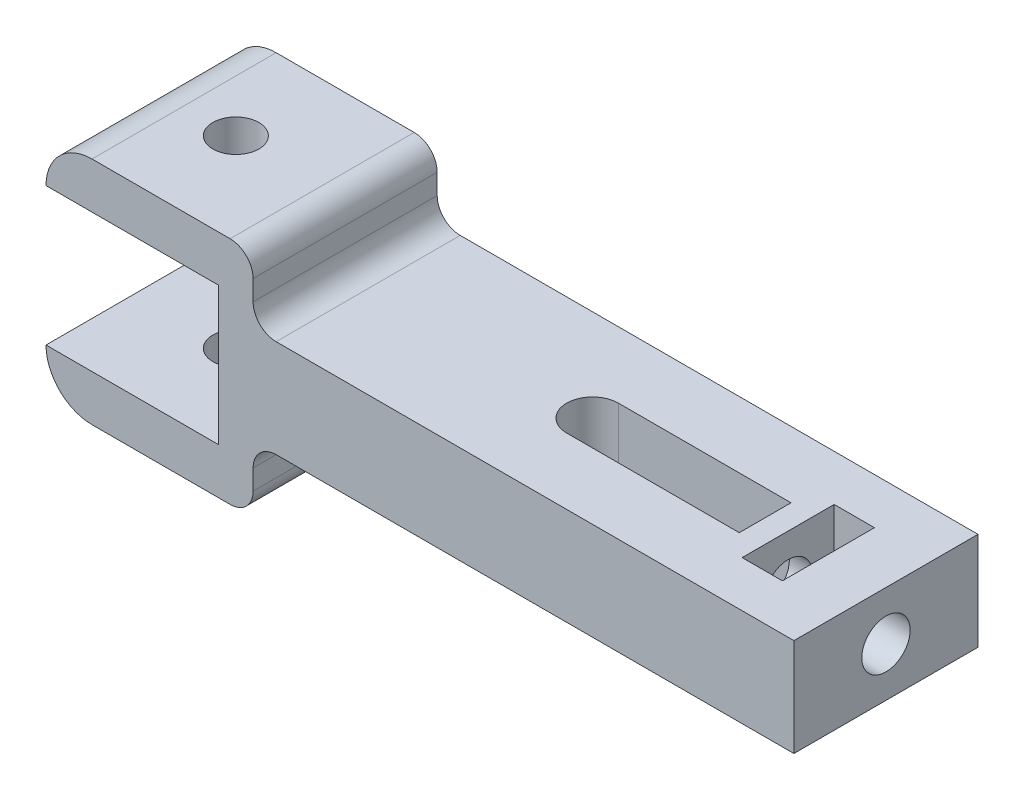
SolidWorks part; units mm, degrees
ref_plane "Front Plane" through (0, 0, 0) normal (0, 0, 1) x (1, 0, 0)
ref_plane "Top Plane" through (0, 0, 0) normal (0, 1, 0) x (1, 0, 0)
ref_plane "Right Plane" through (0, 0, 0) normal (1, 0, 0) x (0, 0, -1)
sketch "Sketch1" plane through (0, 0, 0) normal (0, 0, 1) x (1, 0, 0)
  line L0 (0, 0) -> (-47, 0)
  line L1 (-47, 0) -> (-47, 5.75)
  line L2 (-47, 5.75) -> (-65, 5.75)
  line L3 (-65, 5.75) -> (-65, 1.75)
  line L4 (-65, 1.75) -> (-50, 1.75)
  line L5 (-50, 1.75) -> (-50, -10.25)
  line L6 (0, 0) -> (0, -8.5)
  line L7 (0, -4.25) -> (-50, -4.25) construction
  line L8 (-65, -10.25) -> (-50, -10.25)
  line L9 (-65, -14.25) -> (-65, -10.25)
  line L10 (-47, -14.25) -> (-65, -14.25)
  line L11 (-47, -8.5) -> (-47, -14.25)
  line L12 (0, -8.5) -> (-47, -8.5)
  dimension "D1" = 65
  dimension "D2" = 15
  dimension "D3" = 4.25
  dimension "D4" = 6
  dimension "D5" = 4
  dimension "D6" = 18
extrude "Boss-Extrude1" add sketch "Sketch1" along normal blind 16
sketch "Sketch2" plane through (0, 0, 0) normal (0, 1, 0) x (1, 0, 0)
  line L0 (0, -8) -> (-47, -8) construction
  line L1 (0, -16) -> (0, 0) construction
  line L2 (-47, -16) -> (-47, 0) construction
  line L4 (-8.5, -4) -> (-5, -4)
  line L5 (-8.5, -4) -> (-8.5, -12)
  line L6 (-8.5, -12) -> (-5, -12)
  line L7 (-5, -4) -> (-5, -12)
  line L8 (-8.5, -4) -> (-5, -12) construction
  line L9 (-8.5, -12) -> (-5, -4) construction
  line L10 (-25.5, -10.25) -> (-10.5, -10.25)
  line L12 (-25.5, -5.75) -> (-10.5, -5.75)
  line L13 (-10.5, -10.25) -> (-10.5, -5.75)
  line L14 (-25.5, -10.25) -> (-10.5, -5.75) construction
  line L15 (-25.5, -5.75) -> (-10.5, -10.25) construction
  arc A0 (-25.5, -5.75) -> (-25.5, -10.25) centre (-25.5, -8) ccw
  point P6 (-6.75, -8)
  point P11 (-18, -8)
  dimension "D7" = 2.25
  dimension "D1" = 8
  dimension "D2" = 3.5
  dimension "D3" = 5
  dimension "D4" = 2
  dimension "D5" = 4.5
  dimension "D6" = 15
extrude "Cut-Extrude1" cut sketch "Sketch2" against normal through all
sketch "Sketch3" plane through (0, 0, 0) normal (1, 0, 0) x (0, 0, -1)
  line L0 (-8, 0) -> (-8, -8.5) construction
  line L1 (-16, 0) -> (0, 0) construction
  line L2 (-16, -8.5) -> (0, -8.5) construction
  circle A0 centre (-8, -4.25) radius 2.1
  dimension "D1" = 4.2
extrude "Cut-Extrude2" cut sketch "Sketch3" against normal up to surface (10.5 mm away) up to face at (-10.5, -4.25, 8)
fillet "Fillet1" radius 2 4 edges at (-47, -8.5, 8) (-47, 5.75, 8) (-47, 0, 8) (-47, -14.25, 8)
sketch "Sketch4" plane through (0, -10.25, 0) normal (0, 1, 0) x (1, 0, 0)
  line L0 (-65, -8) -> (-49, -8) construction
  line L1 (-65, -16) -> (-65, 0) construction
  line L2 (-49, 0) -> (-49, -16) construction
  circle A0 centre (-57, -8) radius 9
  dimension "D1" = 18
extrude "Cut-Extrude3" cut sketch "Sketch4" along normal up to surface (12 mm away) up to face at (-57.5, 1.75, 8)
sketch "Sketch5" plane through (0, 5.75, 0) normal (0, 1, 0) x (1, 0, 0)
  line L0 (-65, -8) -> (-49, -8) construction
  line L1 (-65, -16) -> (-65, 0) construction
  line L2 (-49, -16) -> (-49, 0) construction
  circle A0 centre (-56.5, -8) radius 2
  dimension "D1" = 4
  dimension "D2" = 8.5
extrude "Cut-Extrude4" cut sketch "Sketch5" against normal through all
fillet "Fillet2" radius 4 2 edges at (-65, -14.25, 8) (-65, 5.75, 8)
equation "\"X-ROD-SPACING\"=45"
equation "\"Y-ROD-SPACING\"=75"
equation "\"Z-ROD-SPACING\"=17.5"
equation "\"Y-BED-OFFSET\"=2"
equation "\"Y-BED-ROD-INSET\"=3.5"
equation "\"T-SLOT-NUT-FILLET-RADIUS\"=0.25"
equation "\"T-SLOT-SCREW-SHAFT-RADIUS\"=1.75"
equation "\"T-SLOT-SCREW-SHAFT-CUTOUT-LENGTH\"=10.5"
equation "\"T-SLOT-NUT-DEPTH\"=4.2"
equation "\"T-SLOT-NUT-WIDTH\"=3"
equation "\"T-SLOT-NUT-END-DISTANCE\"=8"
equation "\"ACRYLIC-THICKNESS\"=10"
equation "\"ACRYLIC-TAB-CUTOUT-SIZE\"=\"ACRYLIC-THICKNESS\"+\"ACRYLIC-TAB-TOLERANCE\"*2"
equation "\"ACRYLIC-TAB-WIDTH\"=\"ACRYLIC-THICKNESS\""
equation "\"ACRYLIC-M3-HOLE\"=3.2"
equation "\"SMOOTHROD-CAP-SCREW-DISTANCE\"=20"
equation "\"FRAME-WIDTH-INNER\"=370"
equation "\"NEMA17-HOLE-SPACING\"=31"
equation "\"NEMA17-CENTRAL-CUTOUT\"=22.5"
equation "\"Z-BRACKET-REACH\"=55"
equation "\"TOP-BRACKET-SPACING\"=40"
equation "\"SMOOTHROD-X-LENGTH\"=350"
equation "\"SMOOTHROD-Y-LENGTH\"=350"
equation "\"SMOOTHROD-Z-LENGTH\"=350"
equation "\"SMOOTHROD-TIGHTENING-HEADROOM\"=1"
equation "\"LEADSCREW-Z-LENGTH\"=300"
equation "\"SCREW-HEAD-RADIUS\"=6"
equation "\"PRINTED-X-SMOOTHROD-DIAMETER\"=8.2"
equation "\"PRINTED-X-SMOOTHROD-CUTOUT\"=10"
equation "\"PRINTED-X-BASE-HEIGHT\"=10"
equation "\"PRINTED-LM8UU-CUTOUT-SIZE\"=16"
equation "\"PRINTED-LM8UU-CUTOUT-LENGTH\"=24.5"
equation "\"PRINTED-X-IDLER-HEIGHT\"=16"
equation "\"D1@Boss-Extrude1\"=\"PRINTED-X-IDLER-HEIGHT\""
